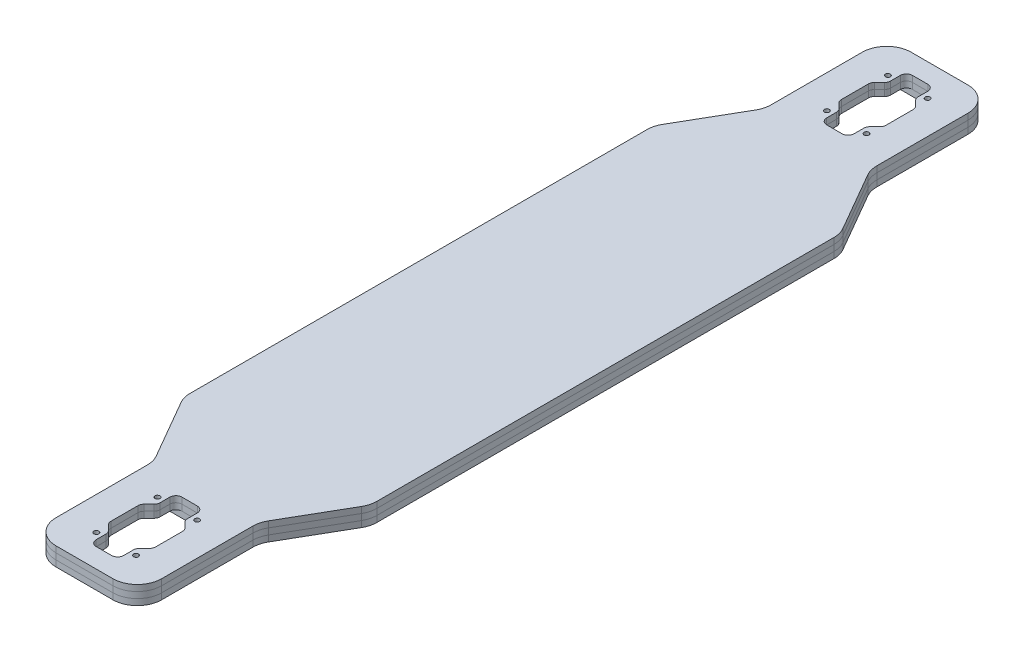
SolidWorks part; units mm, degrees
material "Plywood"
ref_plane "Front Plane" through (0, 0, 0) normal (0, 0, 1) x (1, 0, 0)
ref_plane "Top Plane" through (0, 0, 0) normal (0, 1, 0) x (1, 0, 0)
ref_plane "Right Plane" through (0, 0, 0) normal (1, 0, 0) x (0, 0, -1)
sketch "Sketch1" plane through (0, 0, 0) normal (0, 1, 0) x (1, 0, 0)
  line L0 (-97.155, 0) -> (97.155, 0) construction
  line L1 (0, -444.5) -> (0, 444.5) construction
  line L2 (-97.155, -244.3598) -> (-97.155, 244.3598)
  line L3 (54.9275, 317.5) -> (54.9275, 444.5)
  line L4 (-97.155, 244.3598) -> (-54.9275, 317.5)
  line L5 (-54.9275, 317.5) -> (-54.9275, 444.5)
  line L6 (-54.9275, 444.5) -> (54.9275, 444.5)
  line L7 (97.155, 244.3598) -> (54.9275, 317.5)
  line L8 (97.155, -244.3598) -> (97.155, 244.3598)
  line L9 (97.155, -244.3598) -> (54.9275, -317.5)
  line L10 (54.9275, -317.5) -> (54.9275, -444.5)
  line L11 (-54.9275, -444.5) -> (54.9275, -444.5)
  line L12 (-54.9275, -317.5) -> (-54.9275, -444.5)
  line L13 (-97.155, -244.3598) -> (-54.9275, -317.5)
  line L15 (-20.6375, 411.48) -> (20.6375, 411.48) construction
  line L16 (-20.6375, 411.48) -> (-20.6375, 347.98) construction
  line L17 (-20.6375, 347.98) -> (20.6375, 347.98) construction
  line L18 (20.6375, 411.48) -> (20.6375, 347.98) construction
  circle A0 centre (-20.6375, 411.48) radius 2.54
  circle A1 centre (20.6375, 411.48) radius 2.54
  circle A2 centre (-20.6375, 347.98) radius 2.54
  circle A3 centre (20.6375, 347.98) radius 2.54
  circle A4 centre (-20.6375, -411.48) radius 2.54
  circle A5 centre (-20.6375, -347.98) radius 2.54
  circle A6 centre (20.6375, -347.98) radius 2.54
  circle A7 centre (20.6375, -411.48) radius 2.54
  point P10 (0, 347.98)
  dimension "D5" = 5.08
  dimension "D8" = 30.48
  dimension "D1" = 194.31
  dimension "D2" = 889
  dimension "D3" = 63.5
  dimension "D4" = 41.275
  dimension "D6" = 31.75
  dimension "D7" = 127
  dimension "D9" = 150
extrude "Boss-Extrude1" add sketch "Sketch1" along normal blind 6.35
extrude "Boss-Extrude2" add sketch "Sketch1<2>" along normal blind 6.35 from surface separate body starting at face at (20.6375, 6.35, 345.44)
sketch "Sketch1<2>" plane through (0, 0, 0) normal (0, 1, 0) x (1, 0, 0) same geometry as "Sketch1"
extrude "Boss-Extrude3" add sketch "Sketch1<3>" along normal blind 6.35 from surface separate body starting at face at (0, 12.7, 0)
sketch "Sketch1<3>" plane through (0, 0, 0) normal (0, 1, 0) x (1, 0, 0) same geometry as "Sketch1"
fillet "Fillet1" radius 25.4 12 edges at (54.9275, 15.875, -317.5) (97.155, 15.875, -244.3598) (97.155, 15.875, 244.3598) (54.9275, 15.875, 317.5) (-54.9275, 15.875, 444.5) (-54.9275, 15.875, 317.5) (-97.155, 15.875, 244.3598) (-97.155, 15.875, -244.3598) (-54.9275, 15.875, -317.5) (-54.9275, 15.875, -444.5) (54.9275, 15.875, -444.5) (54.9275, 15.875, 444.5)
fillet "Fillet2" radius 25.4 12 edges at (97.155, 9.525, 244.3598) (54.9275, 9.525, 317.5) (-54.9275, 9.525, 444.5) (-54.9275, 9.525, 317.5) (-97.155, 9.525, 244.3598) (-97.155, 9.525, -244.3598) (-54.9275, 9.525, -317.5) (-54.9275, 9.525, -444.5) (54.9275, 9.525, -444.5) (54.9275, 9.525, -317.5) (97.155, 9.525, -244.3598) (54.9275, 9.525, 444.5)
fillet "Fillet3" radius 25.4 12 edges at (54.9275, 3.175, -444.5) (54.9275, 3.175, -317.5) (97.155, 3.175, -244.3598) (97.155, 3.175, 244.3598) (54.9275, 3.175, 317.5) (-54.9275, 3.175, 444.5) (-54.9275, 3.175, 317.5) (-97.155, 3.175, 244.3598) (-97.155, 3.175, -244.3598) (-54.9275, 3.175, -317.5) (-54.9275, 3.175, -444.5) (54.9275, 3.175, 444.5)
sketch "Sketch2" plane through (0, 0, 0) normal (0, -1, 0) x (1, 0, 0)
  line L0 (18.1842, 309.372) -> (9.0921, 325.12)
  line L1 (-105.7325, 271.526) -> (-96.6404, 287.274)
  line L2 (-96.6404, 287.274) -> (-105.7325, 303.022)
  line L3 (-105.7325, 303.022) -> (-123.9167, 303.022)
  line L4 (-123.9167, 303.022) -> (-133.0088, 287.274)
  line L5 (-133.0088, 287.274) -> (-123.9167, 271.526)
  line L6 (-123.9167, 271.526) -> (-105.7325, 271.526)
  line L7 (9.0921, 325.12) -> (-9.0921, 325.12)
  line L8 (-9.0921, 325.12) -> (-18.1842, 309.372)
  line L9 (-18.1842, 309.372) -> (-9.0921, 293.624)
  line L10 (-9.0921, 293.624) -> (9.0921, 293.624)
  line L11 (9.0921, 293.624) -> (18.1842, 309.372)
  line L12 (-42.2362, 325.12) -> (42.2362, 325.12)
  line L13 (-84.455, 0) -> (84.455, 0) construction
  line L14 (-47.3319, -305.2559) -> (-82.7535, -243.9039)
  line L15 (-42.2362, -325.12) -> (42.2362, -325.12)
  line L16 (82.7535, -243.9039) -> (47.3319, -305.2559)
  line L17 (-29.1827, 271.526) -> (-20.0906, 287.274)
  line L18 (-58.3655, 309.372) -> (-67.4576, 325.12)
  line L19 (-67.4576, 325.12) -> (-85.6418, 325.12)
  line L20 (-85.6418, 325.12) -> (-94.7339, 309.372)
  line L21 (-94.7339, 309.372) -> (-85.6418, 293.624)
  line L22 (-85.6418, 293.624) -> (-67.4576, 293.624)
  line L23 (-67.4576, 293.624) -> (-58.3655, 309.372)
  line L24 (-29.5275, -431.8) -> (29.5275, -431.8)
  line L25 (42.2275, -419.1) -> (42.2275, -324.3059)
  line L26 (47.3319, -305.2559) -> (82.7535, -243.9039)
  line L27 (84.455, -237.5539) -> (84.455, 237.5539)
  line L28 (82.7535, 243.9039) -> (47.3319, 305.2559)
  line L29 (42.2275, 324.3059) -> (42.2275, 419.1)
  line L30 (29.5275, 431.8) -> (-29.5275, 431.8)
  line L31 (-42.2275, 419.1) -> (-42.2275, 324.3059)
  line L32 (-47.3319, 305.2559) -> (-82.7535, 243.9039)
  line L33 (-84.455, 237.5539) -> (-84.455, -237.5539)
  line L34 (-82.7535, -243.9039) -> (-47.3319, -305.2559)
  line L35 (-42.2275, -324.3059) -> (-42.2275, -419.1)
  line L39 (84.455, -237.5539) -> (84.455, 237.5539)
  line L40 (82.7535, 243.9039) -> (47.3319, 305.2559)
  line L44 (-47.3319, 305.2559) -> (-82.7535, 243.9039)
  line L45 (-84.455, 237.5539) -> (-84.455, -237.5539)
  line L46 (-20.0906, 287.274) -> (-29.1827, 303.022)
  line L47 (-29.1827, 303.022) -> (-47.367, 303.022)
  line L48 (-47.367, 303.022) -> (-56.4591, 287.274)
  line L49 (-56.4591, 287.274) -> (-47.367, 271.526)
  line L50 (-47.367, 271.526) -> (-29.1827, 271.526)
  line L51 (94.7339, 309.372) -> (85.6418, 325.12)
  line L52 (85.6418, 325.12) -> (67.4576, 325.12)
  line L53 (67.4576, 325.12) -> (58.3655, 309.372)
  line L54 (58.3655, 309.372) -> (67.4576, 293.624)
  line L55 (67.4576, 293.624) -> (85.6418, 293.624)
  line L56 (85.6418, 293.624) -> (94.7339, 309.372)
  line L57 (47.367, 271.526) -> (56.4591, 287.274)
  line L58 (56.4591, 287.274) -> (47.367, 303.022)
  line L59 (47.367, 303.022) -> (29.1827, 303.022)
  line L60 (29.1827, 303.022) -> (20.0906, 287.274)
  line L61 (20.0906, 287.274) -> (29.1827, 271.526)
  line L62 (29.1827, 271.526) -> (47.367, 271.526)
  line L63 (171.2837, 309.372) -> (162.1915, 325.12)
  line L64 (162.1915, 325.12) -> (144.0073, 325.12)
  line L65 (144.0073, 325.12) -> (134.9152, 309.372)
  line L66 (134.9152, 309.372) -> (144.0073, 293.624)
  line L67 (144.0073, 293.624) -> (162.1915, 293.624)
  line L68 (162.1915, 293.624) -> (171.2837, 309.372)
  line L69 (123.9167, 271.526) -> (133.0088, 287.274)
  line L70 (133.0088, 287.274) -> (123.9167, 303.022)
  line L71 (123.9167, 303.022) -> (105.7325, 303.022)
  line L72 (105.7325, 303.022) -> (96.6404, 287.274)
  line L73 (96.6404, 287.274) -> (105.7325, 271.526)
  line L74 (105.7325, 271.526) -> (123.9167, 271.526)
  line L75 (18.1842, 265.176) -> (9.0921, 280.924)
  line L76 (9.0921, 280.924) -> (-9.0921, 280.924)
  line L77 (-9.0921, 280.924) -> (-18.1842, 265.176)
  line L78 (-18.1842, 265.176) -> (-9.0921, 249.428)
  line L79 (-9.0921, 249.428) -> (9.0921, 249.428)
  line L80 (9.0921, 249.428) -> (18.1842, 265.176)
  line L81 (-29.1827, 227.33) -> (-20.0906, 243.078)
  line L82 (-20.0906, 243.078) -> (-29.1827, 258.826)
  line L83 (-29.1827, 258.826) -> (-47.367, 258.826)
  line L84 (-47.367, 258.826) -> (-56.4591, 243.078)
  line L85 (-56.4591, 243.078) -> (-47.367, 227.33)
  line L86 (-47.367, 227.33) -> (-29.1827, 227.33)
  line L87 (94.7339, 265.176) -> (85.6418, 280.924)
  line L88 (85.6418, 280.924) -> (67.4576, 280.924)
  line L89 (67.4576, 280.924) -> (58.3655, 265.176)
  line L90 (58.3655, 265.176) -> (67.4576, 249.428)
  line L91 (67.4576, 249.428) -> (85.6418, 249.428)
  line L92 (85.6418, 249.428) -> (94.7339, 265.176)
  line L93 (47.367, 227.33) -> (56.4591, 243.078)
  line L94 (56.4591, 243.078) -> (47.367, 258.826)
  line L95 (47.367, 258.826) -> (29.1827, 258.826)
  line L96 (29.1827, 258.826) -> (20.0906, 243.078)
  line L97 (20.0906, 243.078) -> (29.1827, 227.33)
  line L98 (29.1827, 227.33) -> (47.367, 227.33)
  line L99 (171.2837, 265.176) -> (162.1915, 280.924)
  line L100 (162.1915, 280.924) -> (144.0073, 280.924)
  line L101 (144.0073, 280.924) -> (134.9152, 265.176)
  line L102 (134.9152, 265.176) -> (144.0073, 249.428)
  line L103 (144.0073, 249.428) -> (162.1915, 249.428)
  line L104 (162.1915, 249.428) -> (171.2837, 265.176)
  line L105 (123.9167, 227.33) -> (133.0088, 243.078)
  line L106 (133.0088, 243.078) -> (123.9167, 258.826)
  line L107 (123.9167, 258.826) -> (105.7325, 258.826)
  line L108 (105.7325, 258.826) -> (96.6404, 243.078)
  line L109 (96.6404, 243.078) -> (105.7325, 227.33)
  line L110 (105.7325, 227.33) -> (123.9167, 227.33)
  line L111 (18.1842, 220.98) -> (9.0921, 236.728)
  line L112 (9.0921, 236.728) -> (-9.0921, 236.728)
  line L113 (-9.0921, 236.728) -> (-18.1842, 220.98)
  line L114 (-18.1842, 220.98) -> (-9.0921, 205.232)
  line L115 (-9.0921, 205.232) -> (9.0921, 205.232)
  line L116 (9.0921, 205.232) -> (18.1842, 220.98)
  line L117 (-29.1827, 183.134) -> (-20.0906, 198.882)
  line L118 (-20.0906, 198.882) -> (-29.1827, 214.63)
  line L119 (-29.1827, 214.63) -> (-47.367, 214.63)
  line L120 (-47.367, 214.63) -> (-56.4591, 198.882)
  line L121 (-56.4591, 198.882) -> (-47.367, 183.134)
  line L122 (-47.367, 183.134) -> (-29.1827, 183.134)
  line L123 (94.7339, 220.98) -> (85.6418, 236.728)
  line L124 (85.6418, 236.728) -> (67.4576, 236.728)
  line L125 (67.4576, 236.728) -> (58.3655, 220.98)
  line L126 (58.3655, 220.98) -> (67.4576, 205.232)
  line L127 (67.4576, 205.232) -> (85.6418, 205.232)
  line L128 (85.6418, 205.232) -> (94.7339, 220.98)
  line L129 (47.367, 183.134) -> (56.4591, 198.882)
  line L130 (56.4591, 198.882) -> (47.367, 214.63)
  line L131 (47.367, 214.63) -> (29.1827, 214.63)
  line L132 (29.1827, 214.63) -> (20.0906, 198.882)
  line L133 (20.0906, 198.882) -> (29.1827, 183.134)
  line L134 (29.1827, 183.134) -> (47.367, 183.134)
  line L135 (171.2837, 220.98) -> (162.1915, 236.728)
  line L136 (162.1915, 236.728) -> (144.0073, 236.728)
  line L137 (144.0073, 236.728) -> (134.9152, 220.98)
  line L138 (134.9152, 220.98) -> (144.0073, 205.232)
  line L139 (144.0073, 205.232) -> (162.1915, 205.232)
  line L140 (162.1915, 205.232) -> (171.2837, 220.98)
  line L141 (123.9167, 183.134) -> (133.0088, 198.882)
  line L142 (133.0088, 198.882) -> (123.9167, 214.63)
  line L143 (123.9167, 214.63) -> (105.7325, 214.63)
  line L144 (105.7325, 214.63) -> (96.6404, 198.882)
  line L145 (96.6404, 198.882) -> (105.7325, 183.134)
  line L146 (105.7325, 183.134) -> (123.9167, 183.134)
  line L147 (18.1842, 176.784) -> (9.0921, 192.532)
  line L148 (9.0921, 192.532) -> (-9.0921, 192.532)
  line L149 (-9.0921, 192.532) -> (-18.1842, 176.784)
  line L150 (-18.1842, 176.784) -> (-9.0921, 161.036)
  line L151 (-9.0921, 161.036) -> (9.0921, 161.036)
  line L152 (9.0921, 161.036) -> (18.1842, 176.784)
  line L153 (-29.1827, 138.938) -> (-20.0906, 154.686)
  line L154 (-20.0906, 154.686) -> (-29.1827, 170.434)
  line L155 (-29.1827, 170.434) -> (-47.367, 170.434)
  line L156 (-47.367, 170.434) -> (-56.4591, 154.686)
  line L157 (-56.4591, 154.686) -> (-47.367, 138.938)
  line L158 (-47.367, 138.938) -> (-29.1827, 138.938)
  line L159 (94.7339, 176.784) -> (85.6418, 192.532)
  line L160 (85.6418, 192.532) -> (67.4576, 192.532)
  line L161 (67.4576, 192.532) -> (58.3655, 176.784)
  line L162 (58.3655, 176.784) -> (67.4576, 161.036)
  line L163 (67.4576, 161.036) -> (85.6418, 161.036)
  line L164 (85.6418, 161.036) -> (94.7339, 176.784)
  line L165 (47.367, 138.938) -> (56.4591, 154.686)
  line L166 (56.4591, 154.686) -> (47.367, 170.434)
  line L167 (47.367, 170.434) -> (29.1827, 170.434)
  line L168 (29.1827, 170.434) -> (20.0906, 154.686)
  line L169 (20.0906, 154.686) -> (29.1827, 138.938)
  line L170 (29.1827, 138.938) -> (47.367, 138.938)
  line L171 (171.2837, 176.784) -> (162.1915, 192.532)
  line L172 (162.1915, 192.532) -> (144.0073, 192.532)
  line L173 (144.0073, 192.532) -> (134.9152, 176.784)
  line L174 (134.9152, 176.784) -> (144.0073, 161.036)
  line L175 (144.0073, 161.036) -> (162.1915, 161.036)
  line L176 (162.1915, 161.036) -> (171.2837, 176.784)
  line L177 (123.9167, 138.938) -> (133.0088, 154.686)
  line L178 (133.0088, 154.686) -> (123.9167, 170.434)
  line L179 (123.9167, 170.434) -> (105.7325, 170.434)
  line L180 (105.7325, 170.434) -> (96.6404, 154.686)
  line L181 (96.6404, 154.686) -> (105.7325, 138.938)
  line L182 (105.7325, 138.938) -> (123.9167, 138.938)
  line L183 (18.1842, 132.588) -> (9.0921, 148.336)
  line L184 (9.0921, 148.336) -> (-9.0921, 148.336)
  line L185 (-9.0921, 148.336) -> (-18.1842, 132.588)
  line L186 (-18.1842, 132.588) -> (-9.0921, 116.84)
  line L187 (-9.0921, 116.84) -> (9.0921, 116.84)
  line L188 (9.0921, 116.84) -> (18.1842, 132.588)
  line L189 (-29.1827, 94.742) -> (-20.0906, 110.49)
  line L190 (-20.0906, 110.49) -> (-29.1827, 126.238)
  line L191 (-29.1827, 126.238) -> (-47.367, 126.238)
  line L192 (-47.367, 126.238) -> (-56.4591, 110.49)
  line L193 (-56.4591, 110.49) -> (-47.367, 94.742)
  line L194 (-47.367, 94.742) -> (-29.1827, 94.742)
  line L195 (94.7339, 132.588) -> (85.6418, 148.336)
  line L196 (85.6418, 148.336) -> (67.4576, 148.336)
  line L197 (67.4576, 148.336) -> (58.3655, 132.588)
  line L198 (58.3655, 132.588) -> (67.4576, 116.84)
  line L199 (67.4576, 116.84) -> (85.6418, 116.84)
  line L200 (85.6418, 116.84) -> (94.7339, 132.588)
  line L201 (47.367, 94.742) -> (56.4591, 110.49)
  line L202 (56.4591, 110.49) -> (47.367, 126.238)
  line L203 (47.367, 126.238) -> (29.1827, 126.238)
  line L204 (29.1827, 126.238) -> (20.0906, 110.49)
  line L205 (20.0906, 110.49) -> (29.1827, 94.742)
  line L206 (29.1827, 94.742) -> (47.367, 94.742)
  line L207 (171.2837, 132.588) -> (162.1915, 148.336)
  line L208 (162.1915, 148.336) -> (144.0073, 148.336)
  line L209 (144.0073, 148.336) -> (134.9152, 132.588)
  line L210 (134.9152, 132.588) -> (144.0073, 116.84)
  line L211 (144.0073, 116.84) -> (162.1915, 116.84)
  line L212 (162.1915, 116.84) -> (171.2837, 132.588)
  line L213 (123.9167, 94.742) -> (133.0088, 110.49)
  line L214 (133.0088, 110.49) -> (123.9167, 126.238)
  line L215 (123.9167, 126.238) -> (105.7325, 126.238)
  line L216 (105.7325, 126.238) -> (96.6404, 110.49)
  line L217 (96.6404, 110.49) -> (105.7325, 94.742)
  line L218 (105.7325, 94.742) -> (123.9167, 94.742)
  line L219 (18.1842, 88.392) -> (9.0921, 104.14)
  line L220 (9.0921, 104.14) -> (-9.0921, 104.14)
  line L221 (-9.0921, 104.14) -> (-18.1842, 88.392)
  line L222 (-18.1842, 88.392) -> (-9.0921, 72.644)
  line L223 (-9.0921, 72.644) -> (9.0921, 72.644)
  line L224 (9.0921, 72.644) -> (18.1842, 88.392)
  line L225 (-29.1827, 50.546) -> (-20.0906, 66.294)
  line L226 (-20.0906, 66.294) -> (-29.1827, 82.042)
  line L227 (-29.1827, 82.042) -> (-47.367, 82.042)
  line L228 (-47.367, 82.042) -> (-56.4591, 66.294)
  line L229 (-56.4591, 66.294) -> (-47.367, 50.546)
  line L230 (-47.367, 50.546) -> (-29.1827, 50.546)
  line L231 (94.7339, 88.392) -> (85.6418, 104.14)
  line L232 (85.6418, 104.14) -> (67.4576, 104.14)
  line L233 (67.4576, 104.14) -> (58.3655, 88.392)
  line L234 (58.3655, 88.392) -> (67.4576, 72.644)
  line L235 (67.4576, 72.644) -> (85.6418, 72.644)
  line L236 (85.6418, 72.644) -> (94.7339, 88.392)
  line L237 (47.367, 50.546) -> (56.4591, 66.294)
  line L238 (56.4591, 66.294) -> (47.367, 82.042)
  line L239 (47.367, 82.042) -> (29.1827, 82.042)
  line L240 (29.1827, 82.042) -> (20.0906, 66.294)
  line L241 (20.0906, 66.294) -> (29.1827, 50.546)
  line L242 (29.1827, 50.546) -> (47.367, 50.546)
  line L243 (171.2837, 88.392) -> (162.1915, 104.14)
  line L244 (162.1915, 104.14) -> (144.0073, 104.14)
  line L245 (144.0073, 104.14) -> (134.9152, 88.392)
  line L246 (134.9152, 88.392) -> (144.0073, 72.644)
  line L247 (144.0073, 72.644) -> (162.1915, 72.644)
  line L248 (162.1915, 72.644) -> (171.2837, 88.392)
  line L249 (123.9167, 50.546) -> (133.0088, 66.294)
  line L250 (133.0088, 66.294) -> (123.9167, 82.042)
  line L251 (123.9167, 82.042) -> (105.7325, 82.042)
  line L252 (105.7325, 82.042) -> (96.6404, 66.294)
  line L253 (96.6404, 66.294) -> (105.7325, 50.546)
  line L254 (105.7325, 50.546) -> (123.9167, 50.546)
  line L255 (18.1842, 44.196) -> (9.0921, 59.944)
  line L256 (9.0921, 59.944) -> (-9.0921, 59.944)
  line L257 (-9.0921, 59.944) -> (-18.1842, 44.196)
  line L258 (-18.1842, 44.196) -> (-9.0921, 28.448)
  line L259 (-9.0921, 28.448) -> (9.0921, 28.448)
  line L260 (9.0921, 28.448) -> (18.1842, 44.196)
  line L261 (-29.1827, 6.35) -> (-20.0906, 22.098)
  line L262 (-20.0906, 22.098) -> (-29.1827, 37.846)
  line L263 (-29.1827, 37.846) -> (-47.367, 37.846)
  line L264 (-47.367, 37.846) -> (-56.4591, 22.098)
  line L265 (-56.4591, 22.098) -> (-47.367, 6.35)
  line L266 (-47.367, 6.35) -> (-29.1827, 6.35)
  line L267 (94.7339, 44.196) -> (85.6418, 59.944)
  line L268 (85.6418, 59.944) -> (67.4576, 59.944)
  line L269 (67.4576, 59.944) -> (58.3655, 44.196)
  line L270 (58.3655, 44.196) -> (67.4576, 28.448)
  line L271 (67.4576, 28.448) -> (85.6418, 28.448)
  line L272 (85.6418, 28.448) -> (94.7339, 44.196)
  line L273 (47.367, 6.35) -> (56.4591, 22.098)
  line L274 (56.4591, 22.098) -> (47.367, 37.846)
  line L275 (47.367, 37.846) -> (29.1827, 37.846)
  line L276 (29.1827, 37.846) -> (20.0906, 22.098)
  line L277 (20.0906, 22.098) -> (29.1827, 6.35)
  line L278 (29.1827, 6.35) -> (47.367, 6.35)
  line L279 (171.2837, 44.196) -> (162.1915, 59.944)
  line L280 (162.1915, 59.944) -> (144.0073, 59.944)
  line L281 (144.0073, 59.944) -> (134.9152, 44.196)
  line L282 (134.9152, 44.196) -> (144.0073, 28.448)
  line L283 (144.0073, 28.448) -> (162.1915, 28.448)
  line L284 (162.1915, 28.448) -> (171.2837, 44.196)
  line L285 (123.9167, 6.35) -> (133.0088, 22.098)
  line L286 (133.0088, 22.098) -> (123.9167, 37.846)
  line L287 (123.9167, 37.846) -> (105.7325, 37.846)
  line L288 (105.7325, 37.846) -> (96.6404, 22.098)
  line L289 (96.6404, 22.098) -> (105.7325, 6.35)
  line L290 (105.7325, 6.35) -> (123.9167, 6.35)
  line L291 (18.1842, 0) -> (9.0921, 15.748)
  line L292 (9.0921, 15.748) -> (-9.0921, 15.748)
  line L293 (-9.0921, 15.748) -> (-18.1842, 0)
  line L294 (-18.1842, 0) -> (-9.0921, -15.748)
  line L295 (-9.0921, -15.748) -> (9.0921, -15.748)
  line L296 (9.0921, -15.748) -> (18.1842, 0)
  line L297 (-29.1827, -37.846) -> (-20.0906, -22.098)
  line L298 (-20.0906, -22.098) -> (-29.1827, -6.35)
  line L299 (-29.1827, -6.35) -> (-47.367, -6.35)
  line L300 (-47.367, -6.35) -> (-56.4591, -22.098)
  line L301 (-56.4591, -22.098) -> (-47.367, -37.846)
  line L302 (-47.367, -37.846) -> (-29.1827, -37.846)
  line L303 (94.7339, 0) -> (85.6418, 15.748)
  line L304 (85.6418, 15.748) -> (67.4576, 15.748)
  line L305 (67.4576, 15.748) -> (58.3655, 0)
  line L306 (58.3655, 0) -> (67.4576, -15.748)
  line L307 (67.4576, -15.748) -> (85.6418, -15.748)
  line L308 (85.6418, -15.748) -> (94.7339, 0)
  line L309 (47.367, -37.846) -> (56.4591, -22.098)
  line L310 (56.4591, -22.098) -> (47.367, -6.35)
  line L311 (47.367, -6.35) -> (29.1827, -6.35)
  line L312 (29.1827, -6.35) -> (20.0906, -22.098)
  line L313 (20.0906, -22.098) -> (29.1827, -37.846)
  line L314 (29.1827, -37.846) -> (47.367, -37.846)
  line L315 (171.2837, 0) -> (162.1915, 15.748)
  line L316 (162.1915, 15.748) -> (144.0073, 15.748)
  line L317 (144.0073, 15.748) -> (134.9152, 0)
  line L318 (134.9152, 0) -> (144.0073, -15.748)
  line L319 (144.0073, -15.748) -> (162.1915, -15.748)
  line L320 (162.1915, -15.748) -> (171.2837, 0)
  line L321 (123.9167, -37.846) -> (133.0088, -22.098)
  line L322 (133.0088, -22.098) -> (123.9167, -6.35)
  line L323 (123.9167, -6.35) -> (105.7325, -6.35)
  line L324 (105.7325, -6.35) -> (96.6404, -22.098)
  line L325 (96.6404, -22.098) -> (105.7325, -37.846)
  line L326 (105.7325, -37.846) -> (123.9167, -37.846)
  line L327 (18.1842, -44.196) -> (9.0921, -28.448)
  line L328 (9.0921, -28.448) -> (-9.0921, -28.448)
  line L329 (-9.0921, -28.448) -> (-18.1842, -44.196)
  line L330 (-18.1842, -44.196) -> (-9.0921, -59.944)
  line L331 (-9.0921, -59.944) -> (9.0921, -59.944)
  line L332 (9.0921, -59.944) -> (18.1842, -44.196)
  line L333 (-29.1827, -82.042) -> (-20.0906, -66.294)
  line L334 (-20.0906, -66.294) -> (-29.1827, -50.546)
  line L335 (-29.1827, -50.546) -> (-47.367, -50.546)
  line L336 (-47.367, -50.546) -> (-56.4591, -66.294)
  line L337 (-56.4591, -66.294) -> (-47.367, -82.042)
  line L338 (-47.367, -82.042) -> (-29.1827, -82.042)
  line L339 (94.7339, -44.196) -> (85.6418, -28.448)
  line L340 (85.6418, -28.448) -> (67.4576, -28.448)
  line L341 (67.4576, -28.448) -> (58.3655, -44.196)
  line L342 (58.3655, -44.196) -> (67.4576, -59.944)
  line L343 (67.4576, -59.944) -> (85.6418, -59.944)
  line L344 (85.6418, -59.944) -> (94.7339, -44.196)
  line L345 (47.367, -82.042) -> (56.4591, -66.294)
  line L346 (56.4591, -66.294) -> (47.367, -50.546)
  line L347 (47.367, -50.546) -> (29.1827, -50.546)
  line L348 (29.1827, -50.546) -> (20.0906, -66.294)
  line L349 (20.0906, -66.294) -> (29.1827, -82.042)
  line L350 (29.1827, -82.042) -> (47.367, -82.042)
  line L351 (171.2837, -44.196) -> (162.1915, -28.448)
  line L352 (162.1915, -28.448) -> (144.0073, -28.448)
  line L353 (144.0073, -28.448) -> (134.9152, -44.196)
  line L354 (134.9152, -44.196) -> (144.0073, -59.944)
  line L355 (144.0073, -59.944) -> (162.1915, -59.944)
  line L356 (162.1915, -59.944) -> (171.2837, -44.196)
  line L357 (123.9167, -82.042) -> (133.0088, -66.294)
  line L358 (133.0088, -66.294) -> (123.9167, -50.546)
  line L359 (123.9167, -50.546) -> (105.7325, -50.546)
  line L360 (105.7325, -50.546) -> (96.6404, -66.294)
  line L361 (96.6404, -66.294) -> (105.7325, -82.042)
  line L362 (105.7325, -82.042) -> (123.9167, -82.042)
  line L363 (18.1842, -88.392) -> (9.0921, -72.644)
  line L364 (9.0921, -72.644) -> (-9.0921, -72.644)
  line L365 (-9.0921, -72.644) -> (-18.1842, -88.392)
  line L366 (-18.1842, -88.392) -> (-9.0921, -104.14)
  line L367 (-9.0921, -104.14) -> (9.0921, -104.14)
  line L368 (9.0921, -104.14) -> (18.1842, -88.392)
  line L369 (-29.1827, -126.238) -> (-20.0906, -110.49)
  line L370 (-20.0906, -110.49) -> (-29.1827, -94.742)
  line L371 (-29.1827, -94.742) -> (-47.367, -94.742)
  line L372 (-47.367, -94.742) -> (-56.4591, -110.49)
  line L373 (-56.4591, -110.49) -> (-47.367, -126.238)
  line L374 (-47.367, -126.238) -> (-29.1827, -126.238)
  line L375 (94.7339, -88.392) -> (85.6418, -72.644)
  line L376 (85.6418, -72.644) -> (67.4576, -72.644)
  line L377 (67.4576, -72.644) -> (58.3655, -88.392)
  line L378 (58.3655, -88.392) -> (67.4576, -104.14)
  line L379 (67.4576, -104.14) -> (85.6418, -104.14)
  line L380 (85.6418, -104.14) -> (94.7339, -88.392)
  line L381 (47.367, -126.238) -> (56.4591, -110.49)
  line L382 (56.4591, -110.49) -> (47.367, -94.742)
  line L383 (47.367, -94.742) -> (29.1827, -94.742)
  line L384 (29.1827, -94.742) -> (20.0906, -110.49)
  line L385 (20.0906, -110.49) -> (29.1827, -126.238)
  line L386 (29.1827, -126.238) -> (47.367, -126.238)
  line L387 (171.2837, -88.392) -> (162.1915, -72.644)
  line L388 (162.1915, -72.644) -> (144.0073, -72.644)
  line L389 (144.0073, -72.644) -> (134.9152, -88.392)
  line L390 (134.9152, -88.392) -> (144.0073, -104.14)
  line L391 (144.0073, -104.14) -> (162.1915, -104.14)
  line L392 (162.1915, -104.14) -> (171.2837, -88.392)
  line L393 (123.9167, -126.238) -> (133.0088, -110.49)
  line L394 (133.0088, -110.49) -> (123.9167, -94.742)
  line L395 (123.9167, -94.742) -> (105.7325, -94.742)
  line L396 (105.7325, -94.742) -> (96.6404, -110.49)
  line L397 (96.6404, -110.49) -> (105.7325, -126.238)
  line L398 (105.7325, -126.238) -> (123.9167, -126.238)
  line L399 (18.1842, -132.588) -> (9.0921, -116.84)
  line L400 (9.0921, -116.84) -> (-9.0921, -116.84)
  line L401 (-9.0921, -116.84) -> (-18.1842, -132.588)
  line L402 (-18.1842, -132.588) -> (-9.0921, -148.336)
  line L403 (-9.0921, -148.336) -> (9.0921, -148.336)
  line L404 (9.0921, -148.336) -> (18.1842, -132.588)
  line L405 (-29.1827, -170.434) -> (-20.0906, -154.686)
  line L406 (-20.0906, -154.686) -> (-29.1827, -138.938)
  line L407 (-29.1827, -138.938) -> (-47.367, -138.938)
  line L408 (-47.367, -138.938) -> (-56.4591, -154.686)
  line L409 (-56.4591, -154.686) -> (-47.367, -170.434)
  line L410 (-47.367, -170.434) -> (-29.1827, -170.434)
  line L411 (94.7339, -132.588) -> (85.6418, -116.84)
  line L412 (85.6418, -116.84) -> (67.4576, -116.84)
  line L413 (67.4576, -116.84) -> (58.3655, -132.588)
  line L414 (58.3655, -132.588) -> (67.4576, -148.336)
  line L415 (67.4576, -148.336) -> (85.6418, -148.336)
  line L416 (85.6418, -148.336) -> (94.7339, -132.588)
  line L417 (47.367, -170.434) -> (56.4591, -154.686)
  line L418 (56.4591, -154.686) -> (47.367, -138.938)
  line L419 (47.367, -138.938) -> (29.1827, -138.938)
  line L420 (29.1827, -138.938) -> (20.0906, -154.686)
  line L421 (20.0906, -154.686) -> (29.1827, -170.434)
  line L422 (29.1827, -170.434) -> (47.367, -170.434)
  line L423 (171.2837, -132.588) -> (162.1915, -116.84)
  line L424 (162.1915, -116.84) -> (144.0073, -116.84)
  line L425 (144.0073, -116.84) -> (134.9152, -132.588)
  line L426 (134.9152, -132.588) -> (144.0073, -148.336)
  line L427 (144.0073, -148.336) -> (162.1915, -148.336)
  line L428 (162.1915, -148.336) -> (171.2837, -132.588)
  line L429 (123.9167, -170.434) -> (133.0088, -154.686)
  line L430 (133.0088, -154.686) -> (123.9167, -138.938)
  line L431 (123.9167, -138.938) -> (105.7325, -138.938)
  line L432 (105.7325, -138.938) -> (96.6404, -154.686)
  line L433 (96.6404, -154.686) -> (105.7325, -170.434)
  line L434 (105.7325, -170.434) -> (123.9167, -170.434)
  line L435 (18.1842, -176.784) -> (9.0921, -161.036)
  line L436 (9.0921, -161.036) -> (-9.0921, -161.036)
  line L437 (-9.0921, -161.036) -> (-18.1842, -176.784)
  line L438 (-18.1842, -176.784) -> (-9.0921, -192.532)
  line L439 (-9.0921, -192.532) -> (9.0921, -192.532)
  line L440 (9.0921, -192.532) -> (18.1842, -176.784)
  line L441 (-29.1827, -214.63) -> (-20.0906, -198.882)
  line L442 (-20.0906, -198.882) -> (-29.1827, -183.134)
  line L443 (-29.1827, -183.134) -> (-47.367, -183.134)
  line L444 (-47.367, -183.134) -> (-56.4591, -198.882)
  line L445 (-56.4591, -198.882) -> (-47.367, -214.63)
  line L446 (-47.367, -214.63) -> (-29.1827, -214.63)
  line L447 (94.7339, -176.784) -> (85.6418, -161.036)
  line L448 (85.6418, -161.036) -> (67.4576, -161.036)
  line L449 (67.4576, -161.036) -> (58.3655, -176.784)
  line L450 (58.3655, -176.784) -> (67.4576, -192.532)
  line L451 (67.4576, -192.532) -> (85.6418, -192.532)
  line L452 (85.6418, -192.532) -> (94.7339, -176.784)
  line L453 (47.367, -214.63) -> (56.4591, -198.882)
  line L454 (56.4591, -198.882) -> (47.367, -183.134)
  line L455 (47.367, -183.134) -> (29.1827, -183.134)
  line L456 (29.1827, -183.134) -> (20.0906, -198.882)
  line L457 (20.0906, -198.882) -> (29.1827, -214.63)
  line L458 (29.1827, -214.63) -> (47.367, -214.63)
  line L459 (171.2837, -176.784) -> (162.1915, -161.036)
  line L460 (162.1915, -161.036) -> (144.0073, -161.036)
  line L461 (144.0073, -161.036) -> (134.9152, -176.784)
  line L462 (134.9152, -176.784) -> (144.0073, -192.532)
  line L463 (144.0073, -192.532) -> (162.1915, -192.532)
  line L464 (162.1915, -192.532) -> (171.2837, -176.784)
  line L465 (123.9167, -214.63) -> (133.0088, -198.882)
  line L466 (133.0088, -198.882) -> (123.9167, -183.134)
  line L467 (123.9167, -183.134) -> (105.7325, -183.134)
  line L468 (105.7325, -183.134) -> (96.6404, -198.882)
  line L469 (96.6404, -198.882) -> (105.7325, -214.63)
  line L470 (105.7325, -214.63) -> (123.9167, -214.63)
  line L471 (18.1842, -220.98) -> (9.0921, -205.232)
  line L472 (9.0921, -205.232) -> (-9.0921, -205.232)
  line L473 (-9.0921, -205.232) -> (-18.1842, -220.98)
  line L474 (-18.1842, -220.98) -> (-9.0921, -236.728)
  line L475 (-9.0921, -236.728) -> (9.0921, -236.728)
  line L476 (9.0921, -236.728) -> (18.1842, -220.98)
  line L477 (-29.1827, -258.826) -> (-20.0906, -243.078)
  line L478 (-20.0906, -243.078) -> (-29.1827, -227.33)
  line L479 (-29.1827, -227.33) -> (-47.367, -227.33)
  line L480 (-47.367, -227.33) -> (-56.4591, -243.078)
  line L481 (-56.4591, -243.078) -> (-47.367, -258.826)
  line L482 (-47.367, -258.826) -> (-29.1827, -258.826)
  line L483 (94.7339, -220.98) -> (85.6418, -205.232)
  line L484 (85.6418, -205.232) -> (67.4576, -205.232)
  line L485 (67.4576, -205.232) -> (58.3655, -220.98)
  line L486 (58.3655, -220.98) -> (67.4576, -236.728)
  line L487 (67.4576, -236.728) -> (85.6418, -236.728)
  line L488 (85.6418, -236.728) -> (94.7339, -220.98)
  line L489 (47.367, -258.826) -> (56.4591, -243.078)
  line L490 (56.4591, -243.078) -> (47.367, -227.33)
  line L491 (47.367, -227.33) -> (29.1827, -227.33)
  line L492 (29.1827, -227.33) -> (20.0906, -243.078)
  line L493 (20.0906, -243.078) -> (29.1827, -258.826)
  line L494 (29.1827, -258.826) -> (47.367, -258.826)
  line L495 (171.2837, -220.98) -> (162.1915, -205.232)
  line L496 (162.1915, -205.232) -> (144.0073, -205.232)
  line L497 (144.0073, -205.232) -> (134.9152, -220.98)
  line L498 (134.9152, -220.98) -> (144.0073, -236.728)
  line L499 (144.0073, -236.728) -> (162.1915, -236.728)
  line L500 (162.1915, -236.728) -> (171.2837, -220.98)
  line L501 (123.9167, -258.826) -> (133.0088, -243.078)
  line L502 (133.0088, -243.078) -> (123.9167, -227.33)
  line L503 (123.9167, -227.33) -> (105.7325, -227.33)
  line L504 (105.7325, -227.33) -> (96.6404, -243.078)
  line L505 (96.6404, -243.078) -> (105.7325, -258.826)
  line L506 (105.7325, -258.826) -> (123.9167, -258.826)
  line L507 (18.1842, -265.176) -> (9.0921, -249.428)
  line L508 (9.0921, -249.428) -> (-9.0921, -249.428)
  line L509 (-9.0921, -249.428) -> (-18.1842, -265.176)
  line L510 (-18.1842, -265.176) -> (-9.0921, -280.924)
  line L511 (-9.0921, -280.924) -> (9.0921, -280.924)
  line L512 (9.0921, -280.924) -> (18.1842, -265.176)
  line L513 (-29.1827, -303.022) -> (-20.0906, -287.274)
  line L514 (-20.0906, -287.274) -> (-29.1827, -271.526)
  line L515 (-29.1827, -271.526) -> (-47.367, -271.526)
  line L516 (-47.367, -271.526) -> (-56.4591, -287.274)
  line L517 (-56.4591, -287.274) -> (-47.367, -303.022)
  line L518 (-47.367, -303.022) -> (-29.1827, -303.022)
  line L519 (94.7339, -265.176) -> (85.6418, -249.428)
  line L520 (85.6418, -249.428) -> (67.4576, -249.428)
  line L521 (67.4576, -249.428) -> (58.3655, -265.176)
  line L522 (58.3655, -265.176) -> (67.4576, -280.924)
  line L523 (67.4576, -280.924) -> (85.6418, -280.924)
  line L524 (85.6418, -280.924) -> (94.7339, -265.176)
  line L525 (47.367, -303.022) -> (56.4591, -287.274)
  line L526 (56.4591, -287.274) -> (47.367, -271.526)
  line L527 (47.367, -271.526) -> (29.1827, -271.526)
  line L528 (29.1827, -271.526) -> (20.0906, -287.274)
  line L529 (20.0906, -287.274) -> (29.1827, -303.022)
  line L530 (29.1827, -303.022) -> (47.367, -303.022)
  line L531 (171.2837, -265.176) -> (162.1915, -249.428)
  line L532 (162.1915, -249.428) -> (144.0073, -249.428)
  line L533 (144.0073, -249.428) -> (134.9152, -265.176)
  line L534 (134.9152, -265.176) -> (144.0073, -280.924)
  line L535 (144.0073, -280.924) -> (162.1915, -280.924)
  line L536 (162.1915, -280.924) -> (171.2837, -265.176)
  line L537 (123.9167, -303.022) -> (133.0088, -287.274)
  line L538 (133.0088, -287.274) -> (123.9167, -271.526)
  line L539 (123.9167, -271.526) -> (105.7325, -271.526)
  line L540 (105.7325, -271.526) -> (96.6404, -287.274)
  line L541 (96.6404, -287.274) -> (105.7325, -303.022)
  line L542 (105.7325, -303.022) -> (123.9167, -303.022)
  line L543 (18.1842, -309.372) -> (9.0921, -293.624)
  line L544 (9.0921, -293.624) -> (-9.0921, -293.624)
  line L545 (-9.0921, -293.624) -> (-18.1842, -309.372)
  line L546 (-18.1842, -309.372) -> (-9.0921, -325.12)
  line L547 (-9.0921, -325.12) -> (9.0921, -325.12)
  line L548 (9.0921, -325.12) -> (18.1842, -309.372)
  line L549 (-29.1827, -347.218) -> (-20.0906, -331.47)
  line L550 (-20.0906, -331.47) -> (-29.1827, -315.722)
  line L551 (-29.1827, -315.722) -> (-47.367, -315.722)
  line L552 (-47.367, -315.722) -> (-56.4591, -331.47)
  line L553 (-56.4591, -331.47) -> (-47.367, -347.218)
  line L554 (-47.367, -347.218) -> (-29.1827, -347.218)
  line L555 (94.7339, -309.372) -> (85.6418, -293.624)
  line L556 (85.6418, -293.624) -> (67.4576, -293.624)
  line L557 (67.4576, -293.624) -> (58.3655, -309.372)
  line L558 (58.3655, -309.372) -> (67.4576, -325.12)
  line L559 (67.4576, -325.12) -> (85.6418, -325.12)
  line L560 (85.6418, -325.12) -> (94.7339, -309.372)
  line L561 (47.367, -347.218) -> (56.4591, -331.47)
  line L562 (56.4591, -331.47) -> (47.367, -315.722)
  line L563 (47.367, -315.722) -> (29.1827, -315.722)
  line L564 (29.1827, -315.722) -> (20.0906, -331.47)
  line L565 (20.0906, -331.47) -> (29.1827, -347.218)
  line L566 (29.1827, -347.218) -> (47.367, -347.218)
  line L567 (171.2837, -309.372) -> (162.1915, -293.624)
  line L568 (162.1915, -293.624) -> (144.0073, -293.624)
  line L569 (144.0073, -293.624) -> (134.9152, -309.372)
  line L570 (134.9152, -309.372) -> (144.0073, -325.12)
  line L571 (144.0073, -325.12) -> (162.1915, -325.12)
  line L572 (162.1915, -325.12) -> (171.2837, -309.372)
  line L573 (123.9167, -347.218) -> (133.0088, -331.47)
  line L574 (133.0088, -331.47) -> (123.9167, -315.722)
  line L575 (123.9167, -315.722) -> (105.7325, -315.722)
  line L576 (105.7325, -315.722) -> (96.6404, -331.47)
  line L577 (96.6404, -331.47) -> (105.7325, -347.218)
  line L578 (105.7325, -347.218) -> (123.9167, -347.218)
  line L579 (-58.3655, 265.176) -> (-67.4576, 280.924)
  line L580 (-67.4576, 280.924) -> (-85.6418, 280.924)
  line L581 (-85.6418, 280.924) -> (-94.7339, 265.176)
  line L582 (-94.7339, 265.176) -> (-85.6418, 249.428)
  line L583 (-85.6418, 249.428) -> (-67.4576, 249.428)
  line L584 (-67.4576, 249.428) -> (-58.3655, 265.176)
  line L585 (-105.7325, 227.33) -> (-96.6404, 243.078)
  line L586 (-96.6404, 243.078) -> (-105.7325, 258.826)
  line L587 (-105.7325, 258.826) -> (-123.9167, 258.826)
  line L588 (-123.9167, 258.826) -> (-133.0088, 243.078)
  line L589 (-133.0088, 243.078) -> (-123.9167, 227.33)
  line L590 (-123.9167, 227.33) -> (-105.7325, 227.33)
  line L591 (-58.3655, 220.98) -> (-67.4576, 236.728)
  line L592 (-67.4576, 236.728) -> (-85.6418, 236.728)
  line L593 (-85.6418, 236.728) -> (-94.7339, 220.98)
  line L594 (-94.7339, 220.98) -> (-85.6418, 205.232)
  line L595 (-85.6418, 205.232) -> (-67.4576, 205.232)
  line L596 (-67.4576, 205.232) -> (-58.3655, 220.98)
  line L597 (-105.7325, 183.134) -> (-96.6404, 198.882)
  line L598 (-96.6404, 198.882) -> (-105.7325, 214.63)
  line L599 (-105.7325, 214.63) -> (-123.9167, 214.63)
  line L600 (-123.9167, 214.63) -> (-133.0088, 198.882)
  line L601 (-133.0088, 198.882) -> (-123.9167, 183.134)
  line L602 (-123.9167, 183.134) -> (-105.7325, 183.134)
  line L603 (-58.3655, 176.784) -> (-67.4576, 192.532)
  line L604 (-67.4576, 192.532) -> (-85.6418, 192.532)
  line L605 (-85.6418, 192.532) -> (-94.7339, 176.784)
  line L606 (-94.7339, 176.784) -> (-85.6418, 161.036)
  line L607 (-85.6418, 161.036) -> (-67.4576, 161.036)
  line L608 (-67.4576, 161.036) -> (-58.3655, 176.784)
  line L609 (-105.7325, 138.938) -> (-96.6404, 154.686)
  line L610 (-96.6404, 154.686) -> (-105.7325, 170.434)
  line L611 (-105.7325, 170.434) -> (-123.9167, 170.434)
  line L612 (-123.9167, 170.434) -> (-133.0088, 154.686)
  line L613 (-133.0088, 154.686) -> (-123.9167, 138.938)
  line L614 (-123.9167, 138.938) -> (-105.7325, 138.938)
  line L615 (-58.3655, 132.588) -> (-67.4576, 148.336)
  line L616 (-67.4576, 148.336) -> (-85.6418, 148.336)
  line L617 (-85.6418, 148.336) -> (-94.7339, 132.588)
  line L618 (-94.7339, 132.588) -> (-85.6418, 116.84)
  line L619 (-85.6418, 116.84) -> (-67.4576, 116.84)
  line L620 (-67.4576, 116.84) -> (-58.3655, 132.588)
  line L621 (-105.7325, 94.742) -> (-96.6404, 110.49)
  line L622 (-96.6404, 110.49) -> (-105.7325, 126.238)
  line L623 (-105.7325, 126.238) -> (-123.9167, 126.238)
  line L624 (-123.9167, 126.238) -> (-133.0088, 110.49)
  line L625 (-133.0088, 110.49) -> (-123.9167, 94.742)
  line L626 (-123.9167, 94.742) -> (-105.7325, 94.742)
  line L627 (-58.3655, 88.392) -> (-67.4576, 104.14)
  line L628 (-67.4576, 104.14) -> (-85.6418, 104.14)
  line L629 (-85.6418, 104.14) -> (-94.7339, 88.392)
  line L630 (-94.7339, 88.392) -> (-85.6418, 72.644)
  line L631 (-85.6418, 72.644) -> (-67.4576, 72.644)
  line L632 (-67.4576, 72.644) -> (-58.3655, 88.392)
  line L633 (-105.7325, 50.546) -> (-96.6404, 66.294)
  line L634 (-96.6404, 66.294) -> (-105.7325, 82.042)
  line L635 (-105.7325, 82.042) -> (-123.9167, 82.042)
  line L636 (-123.9167, 82.042) -> (-133.0088, 66.294)
  line L637 (-133.0088, 66.294) -> (-123.9167, 50.546)
  line L638 (-123.9167, 50.546) -> (-105.7325, 50.546)
  line L639 (-58.3655, 44.196) -> (-67.4576, 59.944)
  line L640 (-67.4576, 59.944) -> (-85.6418, 59.944)
  line L641 (-85.6418, 59.944) -> (-94.7339, 44.196)
  line L642 (-94.7339, 44.196) -> (-85.6418, 28.448)
  line L643 (-85.6418, 28.448) -> (-67.4576, 28.448)
  line L644 (-67.4576, 28.448) -> (-58.3655, 44.196)
  line L645 (-105.7325, 6.35) -> (-96.6404, 22.098)
  line L646 (-96.6404, 22.098) -> (-105.7325, 37.846)
  line L647 (-105.7325, 37.846) -> (-123.9167, 37.846)
  line L648 (-123.9167, 37.846) -> (-133.0088, 22.098)
  line L649 (-133.0088, 22.098) -> (-123.9167, 6.35)
  line L650 (-123.9167, 6.35) -> (-105.7325, 6.35)
  line L651 (-58.3655, 0) -> (-67.4576, 15.748)
  line L652 (-67.4576, 15.748) -> (-85.6418, 15.748)
  line L653 (-85.6418, 15.748) -> (-94.7339, 0)
  line L654 (-94.7339, 0) -> (-85.6418, -15.748)
  line L655 (-85.6418, -15.748) -> (-67.4576, -15.748)
  line L656 (-67.4576, -15.748) -> (-58.3655, 0)
  line L657 (-105.7325, -37.846) -> (-96.6404, -22.098)
  line L658 (-96.6404, -22.098) -> (-105.7325, -6.35)
  line L659 (-105.7325, -6.35) -> (-123.9167, -6.35)
  line L660 (-123.9167, -6.35) -> (-133.0088, -22.098)
  line L661 (-133.0088, -22.098) -> (-123.9167, -37.846)
  line L662 (-123.9167, -37.846) -> (-105.7325, -37.846)
  line L663 (-58.3655, -44.196) -> (-67.4576, -28.448)
  line L664 (-67.4576, -28.448) -> (-85.6418, -28.448)
  line L665 (-85.6418, -28.448) -> (-94.7339, -44.196)
  line L666 (-94.7339, -44.196) -> (-85.6418, -59.944)
  line L667 (-85.6418, -59.944) -> (-67.4576, -59.944)
  line L668 (-67.4576, -59.944) -> (-58.3655, -44.196)
  line L669 (-105.7325, -82.042) -> (-96.6404, -66.294)
  line L670 (-96.6404, -66.294) -> (-105.7325, -50.546)
  line L671 (-105.7325, -50.546) -> (-123.9167, -50.546)
  line L672 (-123.9167, -50.546) -> (-133.0088, -66.294)
  line L673 (-133.0088, -66.294) -> (-123.9167, -82.042)
  line L674 (-123.9167, -82.042) -> (-105.7325, -82.042)
  line L675 (-58.3655, -88.392) -> (-67.4576, -72.644)
  line L676 (-67.4576, -72.644) -> (-85.6418, -72.644)
  line L677 (-85.6418, -72.644) -> (-94.7339, -88.392)
  line L678 (-94.7339, -88.392) -> (-85.6418, -104.14)
  line L679 (-85.6418, -104.14) -> (-67.4576, -104.14)
  line L680 (-67.4576, -104.14) -> (-58.3655, -88.392)
  line L681 (-105.7325, -126.238) -> (-96.6404, -110.49)
  line L682 (-96.6404, -110.49) -> (-105.7325, -94.742)
  line L683 (-105.7325, -94.742) -> (-123.9167, -94.742)
  line L684 (-123.9167, -94.742) -> (-133.0088, -110.49)
  line L685 (-133.0088, -110.49) -> (-123.9167, -126.238)
  line L686 (-123.9167, -126.238) -> (-105.7325, -126.238)
  line L687 (-58.3655, -132.588) -> (-67.4576, -116.84)
  line L688 (-67.4576, -116.84) -> (-85.6418, -116.84)
  line L689 (-85.6418, -116.84) -> (-94.7339, -132.588)
  line L690 (-94.7339, -132.588) -> (-85.6418, -148.336)
  line L691 (-85.6418, -148.336) -> (-67.4576, -148.336)
  line L692 (-67.4576, -148.336) -> (-58.3655, -132.588)
  line L693 (-105.7325, -170.434) -> (-96.6404, -154.686)
  line L694 (-96.6404, -154.686) -> (-105.7325, -138.938)
  line L695 (-105.7325, -138.938) -> (-123.9167, -138.938)
  line L696 (-123.9167, -138.938) -> (-133.0088, -154.686)
  line L697 (-133.0088, -154.686) -> (-123.9167, -170.434)
  line L698 (-123.9167, -170.434) -> (-105.7325, -170.434)
  line L699 (-58.3655, -176.784) -> (-67.4576, -161.036)
  line L700 (-67.4576, -161.036) -> (-85.6418, -161.036)
  line L701 (-85.6418, -161.036) -> (-94.7339, -176.784)
  line L702 (-94.7339, -176.784) -> (-85.6418, -192.532)
  line L703 (-85.6418, -192.532) -> (-67.4576, -192.532)
  line L704 (-67.4576, -192.532) -> (-58.3655, -176.784)
  line L705 (-105.7325, -214.63) -> (-96.6404, -198.882)
  line L706 (-96.6404, -198.882) -> (-105.7325, -183.134)
  line L707 (-105.7325, -183.134) -> (-123.9167, -183.134)
  line L708 (-123.9167, -183.134) -> (-133.0088, -198.882)
  line L709 (-133.0088, -198.882) -> (-123.9167, -214.63)
  line L710 (-123.9167, -214.63) -> (-105.7325, -214.63)
  line L711 (-58.3655, -220.98) -> (-67.4576, -205.232)
  line L712 (-67.4576, -205.232) -> (-85.6418, -205.232)
  line L713 (-85.6418, -205.232) -> (-94.7339, -220.98)
  line L714 (-94.7339, -220.98) -> (-85.6418, -236.728)
  line L715 (-85.6418, -236.728) -> (-67.4576, -236.728)
  line L716 (-67.4576, -236.728) -> (-58.3655, -220.98)
  line L717 (-105.7325, -258.826) -> (-96.6404, -243.078)
  line L718 (-96.6404, -243.078) -> (-105.7325, -227.33)
  line L719 (-105.7325, -227.33) -> (-123.9167, -227.33)
  line L720 (-123.9167, -227.33) -> (-133.0088, -243.078)
  line L721 (-133.0088, -243.078) -> (-123.9167, -258.826)
  line L722 (-123.9167, -258.826) -> (-105.7325, -258.826)
  line L723 (-58.3655, -265.176) -> (-67.4576, -249.428)
  line L724 (-67.4576, -249.428) -> (-85.6418, -249.428)
  line L725 (-85.6418, -249.428) -> (-94.7339, -265.176)
  line L726 (-94.7339, -265.176) -> (-85.6418, -280.924)
  line L727 (-85.6418, -280.924) -> (-67.4576, -280.924)
  line L728 (-67.4576, -280.924) -> (-58.3655, -265.176)
  line L729 (-105.7325, -303.022) -> (-96.6404, -287.274)
  line L730 (-96.6404, -287.274) -> (-105.7325, -271.526)
  line L731 (-105.7325, -271.526) -> (-123.9167, -271.526)
  line L732 (-123.9167, -271.526) -> (-133.0088, -287.274)
  line L733 (-133.0088, -287.274) -> (-123.9167, -303.022)
  line L734 (-123.9167, -303.022) -> (-105.7325, -303.022)
  line L735 (-58.3655, -309.372) -> (-67.4576, -293.624)
  line L736 (-67.4576, -293.624) -> (-85.6418, -293.624)
  line L737 (-85.6418, -293.624) -> (-94.7339, -309.372)
  line L738 (-94.7339, -309.372) -> (-85.6418, -325.12)
  line L739 (-85.6418, -325.12) -> (-67.4576, -325.12)
  line L740 (-67.4576, -325.12) -> (-58.3655, -309.372)
  line L741 (-105.7325, -347.218) -> (-96.6404, -331.47)
  line L742 (-96.6404, -331.47) -> (-105.7325, -315.722)
  line L743 (-105.7325, -315.722) -> (-123.9167, -315.722)
  line L744 (-123.9167, -315.722) -> (-133.0088, -331.47)
  line L745 (-133.0088, -331.47) -> (-123.9167, -347.218)
  line L746 (-123.9167, -347.218) -> (-105.7325, -347.218)
  line L747 (0, 280.924) -> (0, 293.624) construction
  line L748 (24.6367, 295.148) -> (13.6382, 301.498) construction
  line L749 (-24.6367, 295.148) -> (-13.6382, 301.498) construction
  circle A0 centre (-114.8246, 287.274) radius 15.748 construction
  circle A3 centre (-20.6375, 347.98) radius 2.54 construction
  arc A14 (-47.3319, -305.2559) -> (-42.2362, -325.12) centre (-80.3275, -324.3059) cw
  arc A15 (42.2362, -325.12) -> (47.3319, -305.2559) centre (80.3275, -324.3059) cw
  circle A16 centre (-76.5497, 309.372) radius 15.748 construction
  arc A18 (29.5275, -431.8) -> (42.2275, -419.1) centre (29.5275, -419.1) ccw
  arc A20 (82.7535, -243.9039) -> (84.455, -237.5539) centre (71.755, -237.5539) ccw
  arc A21 (82.7535, -243.9039) -> (84.455, -237.5539) centre (71.755, -237.5539) ccw
  arc A22 (84.455, 237.5539) -> (82.7535, 243.9039) centre (71.755, 237.5539) ccw
  arc A23 (84.455, 237.5539) -> (82.7535, 243.9039) centre (71.755, 237.5539) ccw
  arc A24 (47.3319, -305.2559) -> (42.2275, -324.3059) centre (80.3275, -324.3059) ccw
  arc A25 (42.2275, 324.3059) -> (47.3319, 305.2559) centre (80.3275, 324.3059) ccw
  arc A26 (-47.3319, 305.2559) -> (-42.2275, 324.3059) centre (-80.3275, 324.3059) ccw
  arc A27 (-42.2275, -324.3059) -> (-47.3319, -305.2559) centre (-80.3275, -324.3059) ccw
  arc A29 (42.2362, 325.12) -> (47.3319, 305.2559) centre (80.3275, 324.3059) ccw
  arc A30 (-47.3319, 305.2559) -> (-42.2362, 325.12) centre (-80.3275, 324.3059) ccw
  arc A31 (42.2275, 419.1) -> (29.5275, 431.8) centre (29.5275, 419.1) ccw
  arc A33 (-29.5275, 431.8) -> (-42.2275, 419.1) centre (-29.5275, 419.1) ccw
  arc A35 (-82.7535, 243.9039) -> (-84.455, 237.5539) centre (-71.755, 237.5539) ccw
  arc A36 (-82.7535, 243.9039) -> (-84.455, 237.5539) centre (-71.755, 237.5539) ccw
  arc A37 (-84.455, -237.5539) -> (-82.7535, -243.9039) centre (-71.755, -237.5539) ccw
  arc A38 (-84.455, -237.5539) -> (-82.7535, -243.9039) centre (-71.755, -237.5539) ccw
  arc A39 (-42.2275, -419.1) -> (-29.5275, -431.8) centre (-29.5275, -419.1) ccw
  point P2 (0, 293.624)
  point P20 (0, 325.12)
  dimension "D2" = 12.7
  dimension "D3" = 20.32
  dimension "D1" = 12.7
  dimension "D5" = 4
  dimension "D4" = 15
extrude "Cut-Extrude1" cut sketch "Sketch2" against normal blind 12.7 contours L10 L11 L0 L7 L8 L9 | L44 L50 L17 L46 L47 | L85 L86 L81 L82 L83 L84 L44 | L79 L80 L75 L76 L77 L78 | L61 L62 L40 L59 L60 | L97 L98 L93 L40 L94 L95 L96 | L126 L127 L40 L125 | L133 L134 L129 L130 L131 L132 | L115 L116 L111 L112 L113 L114 | L121 L122 L117 L118 L119 L120 | L595 L596 L591 L44 | L607 L608 L603 L604 L45 | L157 L158 L153 L154 L155 L156 | L619 L620 L615 L616 L45 | L193 L194 L189 L190 L191 L192 | L187 L188 L183 L184 L185 L186 | L151 L152 L147 L148 L149 L150 | L169 L170 L165 L166 L167 L168 | L162 L163 L39 L160 L161 | L198 L199 L39 L196 L197 | L205 L206 L201 L202 L203 L204 | L223 L224 L219 L220 L221 L222 | L229 L230 L225 L226 L227 L228 | L265 L266 L261 L262 L263 L264 | L643 L644 L639 L640 L45 | L259 L260 L255 L256 L257 L258 | L241 L242 L237 L238 L239 L240 | L234 L235 L39 L232 L233 | L270 L271 L39 L268 L269 | L277 L278 L273 L274 L275 L276 | L301 L302 L297 L298 L299 L300 | L655 L656 L651 L652 L45 | L295 L296 L291 L292 L293 L294 | L313 L314 L309 L310 L311 L312 | L306 L307 L39 L304 L305 | L342 L343 L39 L340 L341 | L349 L350 L345 L346 L347 L348 | L331 L332 L327 L328 L329 L330 | L337 L338 L333 L334 L335 L336 | L667 L668 L663 L664 L45 | L367 L368 L363 L364 L365 L366 | L373 L374 L369 L370 L371 L372 | L679 L680 L675 L676 L45 | L385 L386 L381 L382 L383 L384 | L378 L379 L39 L376 L377 | L414 L415 L39 L412 L413 | L403 L404 L399 L400 L401 L402 | L421 L422 L417 L418 L419 L420 | L439 L440 L435 L436 L437 L438 | L409 L410 L405 L406 L407 L408 | L691 L692 L687 L688 L45 | L703 L704 L699 L700 L45 | L457 L458 L453 L454 L455 L456 | L445 L446 L441 L442 L443 L444 | L475 L476 L471 L472 L473 L474 | L450 L451 L39 L448 L449 | L485 L486 L16 L484 | L14 L716 L711 L712 | L481 L482 L477 L478 L479 L480 L14 | L511 L512 L507 L508 L509 L510 | L493 L494 L489 L16 L490 L491 L492 | L529 L530 L16 L527 L528 | L14 L518 L513 L514 L515 | L15 L548 L543 L544 L545 L546 | L631 L632 L627 L628 L45 | L583 L584 L579 L44 | L90 L91 L40 L89 | L14 L728 L723 L724 | L521 L522 L16 L520 region at (0, 0, 309.372) region at (67.8295, 0, 260.1414) region at (-67.8295, 0, 260.1414) region at (73.5234, 0, 220.98) region at (-73.5234, 0, 220.98) region at (73.5234, 0, 176.784) region at (-73.5234, 0, 176.784) region at (73.5234, 0, 132.588) region at (-73.5234, 0, 132.588) region at (73.5234, 0, 88.392) region at (-73.5234, 0, 88.392) region at (73.5234, 0, 44.196) region at (-73.5234, 0, 44.196) region at (73.5234, 0, 0) region at (-73.5234, 0, 0) region at (73.5234, 0, -44.196) region at (-73.5234, 0, -44.196) region at (73.5234, 0, -88.392) region at (-73.5234, 0, -88.392) region at (73.5234, 0, -132.588) region at (-73.5234, 0, -132.588) region at (73.5234, 0, -176.784) region at (-73.5234, 0, -176.784) region at (73.5234, 0, -220.98) region at (-73.5234, 0, -220.98) region at (67.8295, 0, -260.1414) region at (-67.8295, 0, -260.1414) region at (0, 0, -309.372) region at (-38.2749, 0, 287.274) region at (38.2749, 0, 287.274) region at (0, 0, 265.176) region at (-38.2749, 0, 243.078) region at (38.2749, 0, 243.078) region at (0, 0, 220.98) region at (-38.2749, 0, 198.882) region at (38.2749, 0, 198.882) region at (0, 0, 176.784) region at (-38.2749, 0, 154.686) region at (38.2749, 0, 154.686) region at (0, 0, 132.588) region at (-38.2749, 0, 110.49) region at (38.2749, 0, 110.49) region at (0, 0, 88.392) region at (-38.2749, 0, 66.294) region at (38.2749, 0, 66.294) region at (0, 0, 44.196) region at (-38.2749, 0, 22.098) region at (38.2749, 0, 22.098) region at (0, 0, 0) region at (-38.2749, 0, -22.098) region at (38.2749, 0, -22.098) region at (0, 0, -44.196) region at (-38.2749, 0, -66.294) region at (38.2749, 0, -66.294) region at (0, 0, -88.392) region at (-38.2749, 0, -110.49) region at (38.2749, 0, -110.49) region at (0, 0, -132.588) region at (-38.2749, 0, -154.686) region at (38.2749, 0, -154.686)
sketch "Sketch5" plane through (0, 0, 0) normal (0, -1, 0) x (1, 0, 0)
  line L0 (-20.6375, 411.48) -> (20.6375, 411.48) construction
  line L1 (0, 411.48) -> (0, 347.98) construction
  line L2 (-14.2875, 424.3076) -> (-14.2875, 405.2576)
  line L3 (-14.2875, 405.2576) -> (-23.1775, 396.3676)
  line L4 (-23.1775, 396.3676) -> (-23.1775, 363.0924)
  line L5 (-23.1775, 379.73) -> (0, 379.73) construction
  line L6 (-20.6375, 347.98) -> (20.6375, 347.98) construction
  line L7 (-14.2875, 424.3076) -> (14.2875, 424.3076)
  line L8 (14.2875, 424.3076) -> (14.2875, 405.2576)
  line L9 (14.2875, 405.2576) -> (23.1775, 396.3676)
  line L10 (23.1775, 396.3676) -> (23.1775, 363.0924)
  line L11 (14.2875, 354.2024) -> (23.1775, 363.0924)
  line L12 (14.2875, 335.1524) -> (14.2875, 354.2024)
  line L13 (-14.2875, 335.1524) -> (14.2875, 335.1524)
  line L14 (-14.2875, 335.1524) -> (-14.2875, 354.2024)
  line L15 (-14.2875, 354.2024) -> (-23.1775, 363.0924)
  line L16 (55, 0) -> (-55, 0) construction
  line L17 (-30.7975, 424.3076) -> (30.7975, 424.3076)
  line L18 (-30.7975, 424.3076) -> (-30.7975, 335.1524)
  line L19 (-30.7975, 335.1524) -> (30.7975, 335.1524)
  line L20 (30.7975, 424.3076) -> (30.7975, 335.1524)
  line L21 (-30.7975, -335.1524) -> (30.7975, -335.1524)
  line L22 (30.7975, -424.3076) -> (30.7975, -335.1524)
  line L23 (-30.7975, -424.3076) -> (30.7975, -424.3076)
  line L24 (-30.7975, -424.3076) -> (-30.7975, -335.1524)
  line L25 (14.2875, -405.2576) -> (23.1775, -396.3676)
  line L26 (14.2875, -424.3076) -> (14.2875, -405.2576)
  line L27 (-14.2875, -424.3076) -> (14.2875, -424.3076)
  line L28 (-14.2875, -424.3076) -> (-14.2875, -405.2576)
  line L29 (-14.2875, -405.2576) -> (-23.1775, -396.3676)
  line L30 (-23.1775, -396.3676) -> (-23.1775, -363.0924)
  line L31 (-14.2875, -354.2024) -> (-23.1775, -363.0924)
  line L32 (-14.2875, -335.1524) -> (-14.2875, -354.2024)
  line L33 (-14.2875, -335.1524) -> (14.2875, -335.1524)
  line L34 (14.2875, -335.1524) -> (14.2875, -354.2024)
  line L35 (14.2875, -354.2024) -> (23.1775, -363.0924)
  line L36 (23.1775, -396.3676) -> (23.1775, -363.0924)
  circle A0 centre (-20.6375, 411.48) radius 2.54 construction
  point P20 (0, 424.3076)
  point P25 (23.1775, 379.73)
  dimension "D1" = 6.35
  dimension "D2" = 6.35
  dimension "D3" = 135
  dimension "D4" = 19.05
  dimension "D5" = 7.62
extrude "Cut-Extrude2" cut sketch "Sketch5" against normal through all contours L15 L14 L13 L12 L11 L10 L9 L8 L7 L2 L3 L4 | L25 L36 L35 L34 L21 L32 L31 L30 L29 L28 L23 L26 region at (0, 0, 379.73) region at (0, 0, -379.73)
extrude "Cut-Extrude3" cut sketch "Sketch5<3>" against normal blind 6.35 contours L17 L18 L3 L2 | L20 L17 L8 L9 | L20 L11 L12 L19 | L18 L19 L14 L15 | L32 L21 L24 L23 L28 L29 L30 L31 | L36 L25 L26 L23 L22 L21 L34 L35 region at (-23.951, 0, 379.73) region at (23.951, 0, 379.73) region at (-23.951, 0, -379.73) region at (23.951, 0, -379.73)
sketch "Sketch5<3>" plane through (0, 0, 0) normal (0, -1, 0) x (1, 0, 0) same geometry as "Sketch5"
fillet "Fillet4" radius 6.35 24 edges at (-23.1775, 15.875, 396.3676) (-14.2875, 15.875, 405.2576) (14.2875, 15.875, 424.3076) (14.2875, 15.875, 405.2576) (23.1775, 15.875, 396.3676) (23.1775, 15.875, 363.0924) (14.2875, 15.875, 354.2024) (14.2875, 15.875, 335.1524) (-14.2875, 15.875, 335.1524) (-14.2875, 15.875, 354.2024) (-23.1775, 15.875, 363.0924) (-14.2875, 15.875, 424.3076) (14.2875, 15.875, -405.2576) (14.2875, 15.875, -424.3076) (-14.2875, 15.875, -405.2576) (-23.1775, 15.875, -396.3676) (-23.1775, 15.875, -363.0924) (-14.2875, 15.875, -354.2024) (-14.2875, 15.875, -335.1524) (14.2875, 15.875, -335.1524) (14.2875, 15.875, -354.2024) (23.1775, 15.875, -363.0924) (23.1775, 15.875, -396.3676) (-14.2875, 15.875, -424.3076)
fillet "Fillet5" radius 6.35 24 edges at (-23.1775, 9.525, 363.0924) (-23.1775, 9.525, 396.3676) (-14.2875, 9.525, 405.2576) (14.2875, 9.525, 424.3076) (14.2875, 9.525, 405.2576) (23.1775, 9.525, 396.3676) (23.1775, 9.525, 363.0924) (14.2875, 9.525, 354.2024) (14.2875, 9.525, 335.1524) (-14.2875, 9.525, 335.1524) (-14.2875, 9.525, 354.2024) (-14.2875, 9.525, 424.3076) (14.2875, 9.525, -424.3076) (-14.2875, 9.525, -405.2576) (-23.1775, 9.525, -396.3676) (-23.1775, 9.525, -363.0924) (-14.2875, 9.525, -354.2024) (-14.2875, 9.525, -335.1524) (14.2875, 9.525, -335.1524) (14.2875, 9.525, -354.2024) (23.1775, 9.525, -363.0924) (23.1775, 9.525, -396.3676) (14.2875, 9.525, -405.2576) (-14.2875, 9.525, -424.3076)
fillet "Fillet6" radius 8.89 8 edges at (30.7975, 3.175, 424.3076) (30.7975, 3.175, 335.1524) (-30.7975, 3.175, 335.1524) (-30.7975, 3.175, 424.3076) (-30.7975, 3.175, -335.1524) (30.7975, 3.175, -335.1524) (30.7975, 3.175, -424.3076) (-30.7975, 3.175, -424.3076)
